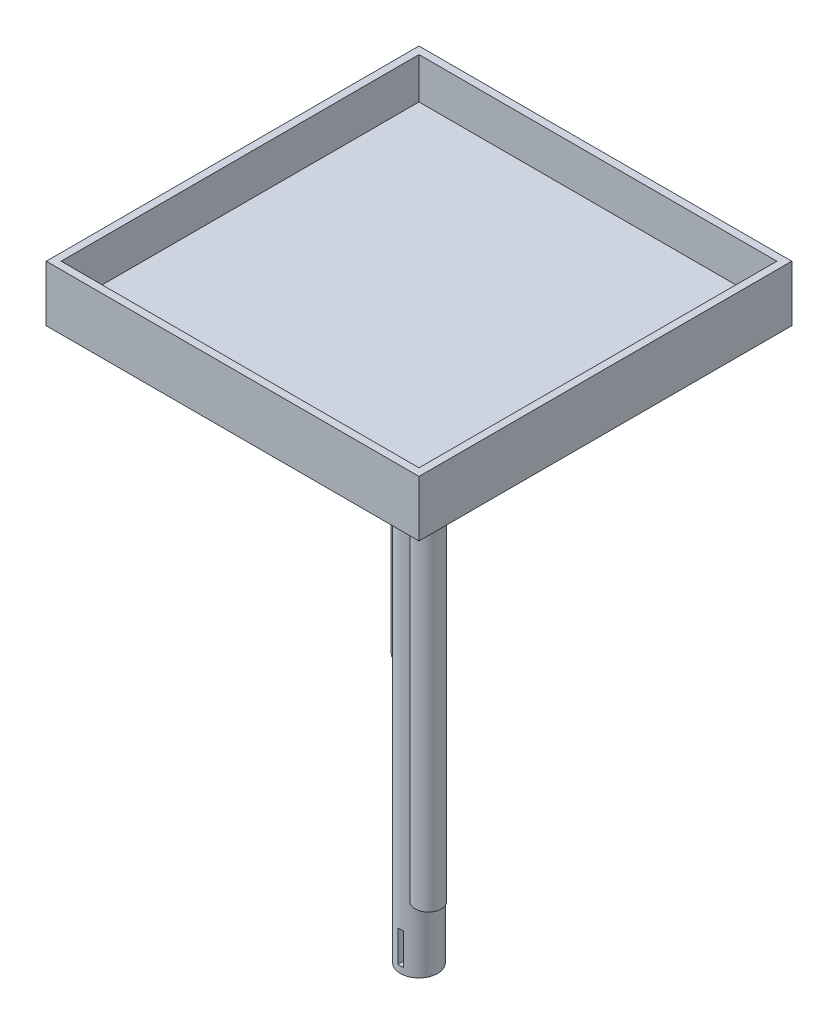
SolidWorks part; units mm, degrees
ref_plane "Plano frontal" through (0, 0, 0) normal (0, 0, 1) x (1, 0, 0)
ref_plane "Plano superior" through (0, 0, 0) normal (0, 1, 0) x (1, 0, 0)
ref_plane "Plano direito" through (0, 0, 0) normal (1, 0, 0) x (0, 0, -1)
sketch "Esboço1" plane through (0, 0, 0) normal (0, 1, 0) x (1, 0, 0)
  line L1 (-50, -50) -> (50, -50)
  line L2 (-50, -50) -> (-50, 50)
  line L3 (-50, 50) -> (50, 50)
  line L4 (50, -50) -> (50, 50)
  line L5 (-50, -50) -> (50, 50) construction
  line L6 (-50, 50) -> (50, -50) construction
  point P0 (0, 0)
  dimension "D1" = 100
  dimension "D2" = 100
extrude "Ressalto-extrusão1" add sketch "Esboço1" along normal blind 15
sketch "Esboço2" plane through (0, 15, 0) normal (0, 1, 0) x (1, 0, 0)
  line L1 (-48, -48) -> (48, -48)
  line L2 (-48, -48) -> (-48, 48)
  line L3 (-48, 48) -> (48, 48)
  line L4 (48, -48) -> (48, 48)
  line L5 (-48, -48) -> (48, 48) construction
  line L6 (-48, 48) -> (48, -48) construction
  point P0 (0, 0)
  dimension "D1" = 96
  dimension "D2" = 96
extrude "Corte-extrusão1" cut sketch "Esboço2" against normal blind 11
sketch "Esboço3" plane through (0, 0, 0) normal (0, -1, 0) x (-1, 0, 0)
  circle A0 centre (0, 0) radius 5
  dimension "D1" = 10
extrude "Ressalto-extrusão2" add sketch "Esboço3" along normal blind 148
sketch "Esboço5" plane through (0, 0, -50) normal (0, 0, -1) x (-1, 0, 0)
  line L0 (-50, 0) -> (50, 0) construction
  line L1 (0.725, -137.75) -> (-0.725, -137.75)
  line L2 (0.725, -137.75) -> (0.725, -146.25)
  line L3 (0.725, -146.25) -> (-0.725, -146.25)
  line L4 (-0.725, -137.75) -> (-0.725, -146.25)
  line L5 (0.725, -137.75) -> (-0.725, -146.25) construction
  line L6 (0.725, -146.25) -> (-0.725, -137.75) construction
  line L7 (50, 15) -> (50, 0) construction
  point P0 (0, -142)
  dimension "D1" = 8.5
  dimension "D2" = 1.45
  dimension "D3" = 142
  dimension "D4" = 50
extrude "Corte-extrusão2" cut sketch "Esboço5" against normal through all
sketch "Esboço7" plane through (0, 0, 0) normal (0, -1, 0) x (1, 0, 0)
  circle A0 centre (30, 27.5) radius 3.5
  circle A1 centre (-30, -27.5) radius 3.5
  dimension "D2" = 7
  dimension "D4" = 7
  dimension "D1" = 30
  dimension "D3" = 27.5
  dimension "D5" = 30
  dimension "D6" = 27.5
extrude "Ressalto-extrusão3" add sketch "Esboço7" along normal blind 105
fillet "Filete2" radius 5 1 edges at (-30, 0, -31)
fillet "Filete3" radius 5 1 edges at (30, 0, 24)
fillet "Filete4" radius 5 1 edges at (0, 0, -5)
